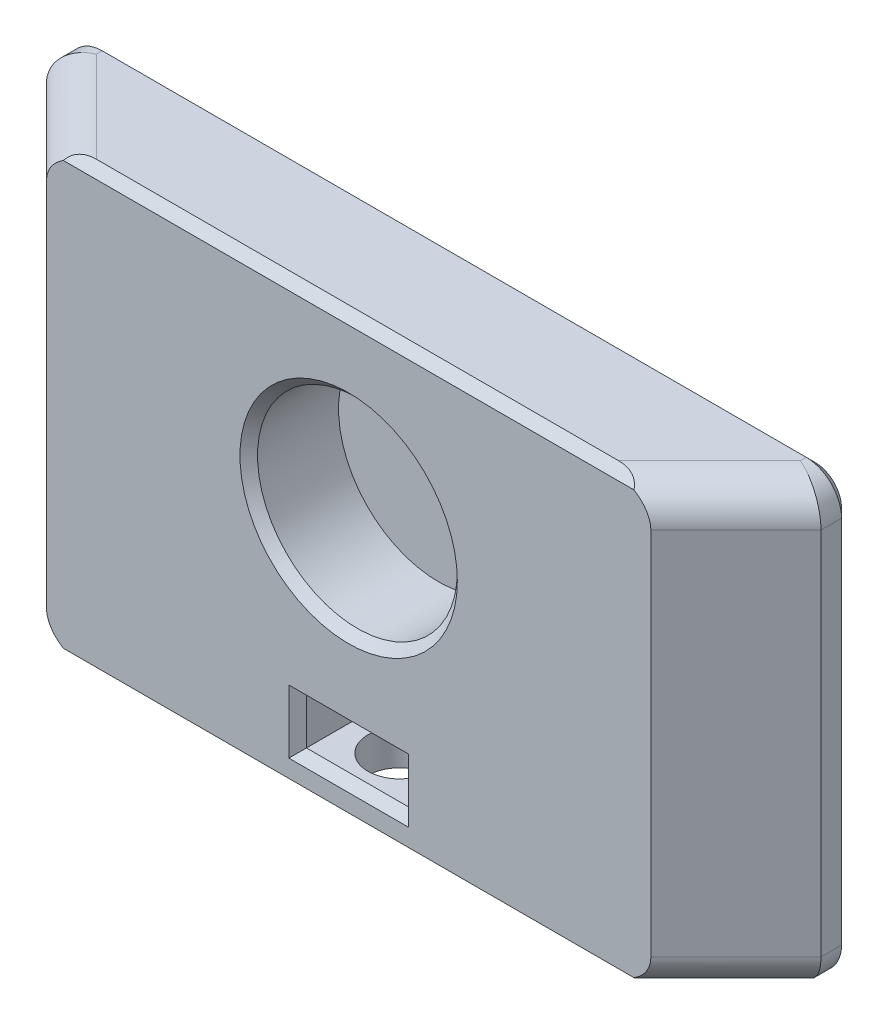
SolidWorks part; units mm, degrees
ref_plane "Front" through (0, 0, 0) normal (0, 0, 1) x (1, 0, 0)
ref_plane "Top" through (0, 0, 0) normal (0, 1, 0) x (1, 0, 0)
ref_plane "Right" through (0, 0, 0) normal (1, 0, 0) x (0, 0, -1)
sketch "Skizze1" plane through (0, 0, 0) normal (0, 0, 1) x (1, 0, 0)
  line L0 (22, 10) -> (-22, 10)
  line L1 (-22, -15) -> (22, -15)
  line L2 (-22, -15) -> (-22, 10)
  line L3 (-22, 15) -> (22, 15) construction
  line L4 (22, -15) -> (22, 10)
  line L5 (-22, -15) -> (22, 15) construction
  line L6 (-22, 15) -> (22, -15) construction
  line L7 (-22, 10) -> (-22, 15) construction
  line L8 (22, 10) -> (22, 15) construction
  point P0 (0, 0)
  dimension "D1" = 44
  dimension "D2" = 30
  dimension "D3" = 5
extrude "Aufsatz-Linear austragen1" add sketch "Skizze1" along normal blind 6.5
sketch "Skizze2" plane through (0, 0, 6.5) normal (0, 0, 1) x (1, 0, 0)
  circle A0 centre (0, 0) radius 5.675
  dimension "D1" = 11.35
extrude "Schnitt-Linear austragen1" cut sketch "Skizze2" against normal blind 5.1
fillet "Verrundung1" radius 2 4 edges at (22, 10, 3.25) (22, -15, 3.25) (-22, 10, 3.25) (-22, -15, 3.25)
sketch "Skizze8" plane through (0, 0, 6.5) normal (0, 0, 1) x (1, 0, 0)
  line L0 (0, 0) -> (0, -19.4862) construction
  line L1 (-2.9, -13) -> (2.9, -13)
  line L2 (2.9, -13) -> (2.9, -10.4)
  line L3 (2.9, -10.4) -> (-2.9, -10.4)
  line L4 (-20, -15) -> (20, -15) construction
  line L5 (-2.9, -13) -> (-2.9, -10.4)
  point P10 (0, -10.4)
  point P11 (0, -13)
  dimension "D1" = 2.6
  dimension "D2" = 2
  dimension "D3" = 5.8
extrude "Schnitt-Linear austragen5" cut sketch "Skizze8" against normal offset from surface (4.5 mm away) 2 up to face at (0, -2.5, 0)
sketch "Skizze9" plane through (0, -10.4, 0) normal (0, -1, 0) x (1, 0, 0)
  line L0 (-2.775, 2) -> (0, 0.3979)
  line L1 (0, 0) -> (0, 8.8539) construction
  line L2 (-20, 0) -> (20, 0) construction
  line L3 (2.775, 2) -> (0, 0.3979)
  line L4 (-2.775, 2) -> (2.775, 2)
  line L5 (2.775, 2) -> (2.775, 5.2043) construction
  line L6 (2.775, 5.2043) -> (0, 6.8064) construction
  line L7 (-2.775, 5.2043) -> (0, 6.8064) construction
  line L8 (-2.775, 2) -> (-2.775, 5.2043) construction
  line L9 (-2.775, 5.2043) -> (2.775, 2) construction
  circle A0 centre (0, 3.6021) radius 1.8
  line M6 (-2.9, 2) -> (2.9, 2)
  dimension "D4" = 3.6
  dimension "D1" = 5.55
  dimension "D2" = 2
  dimension "D3" = 120
extrude "Schnitt-Linear austragen6" cut sketch "Skizze9" along normal up to surface (2.6 mm away) contours A0 L0 L3 M6 | L4 A0 region at (0, -10.4, 1.4424) region at (0, -10.4, 1.9205) up to face at (0, -13, 4.25)
extrude "Schnitt-Linear austragen7" cut sketch "Skizze9<3>" along normal through all and the other way blind 4.1 contours L4 A0 | L4 A0 region at (0, -10.4, 3.6391) region at (0, -10.4, 1.9205)
sketch "Skizze9<3>" plane through (0, -10.4, 0) normal (0, -1, 0) x (1, 0, 0) same geometry as "Skizze9"
sketch "Skizze10" plane through (0, -15, 0) normal (0, -1, 0) x (1, 0, 0)
  line L0 (-22, 1.6672) -> (-17.1672, 6.5)
  line L1 (-22, 0) -> (-22, 6.5) construction
  line L2 (-20, 6.5) -> (20, 6.5) construction
  line L3 (-17.15, 6.8) -> (-22.15, 1.8) construction
  line L6 (0, 0) -> (0, -3.8507) construction
  line L7 (-22, 1.6672) -> (-22, 6.5)
  line L8 (-22, 6.5) -> (-17.1672, 6.5)
  line L9 (22, 1.6672) -> (22, 6.5)
  line L10 (22, 1.6672) -> (17.1672, 6.5)
  line L11 (22, 6.5) -> (17.1672, 6.5)
  dimension "D1" = 0.2
extrude "Schnitt-Linear austragen8" cut sketch "Skizze10" against normal through all
chamfer "Fase1" distance 0.5 angle 45 15 edges at (0, -15, 6.5) (0, 10, 6.5) (5.675, 0, 6.5) (0, -10.4, 6.5) (-2.9, -11.7, 6.5) (0, -13, 6.5) (2.9, -11.7, 6.5) (-21.4142, 9.4142, 0) (-22, -2.5, 0) (-21.4142, -14.4142, 0) (0, -15, 0) (21.4142, -14.4142, 0) (22, -2.5, 0) (21.4142, 9.4142, 0) (0, 10, 0)
fillet "Verrundung2" radius 2 4 edges at (-18.8336, 10, 4.8336) (18.8336, 10, 4.8336) (18.8336, -15, 4.8336) (-18.8336, -15, 4.8336) tangent propagation no
